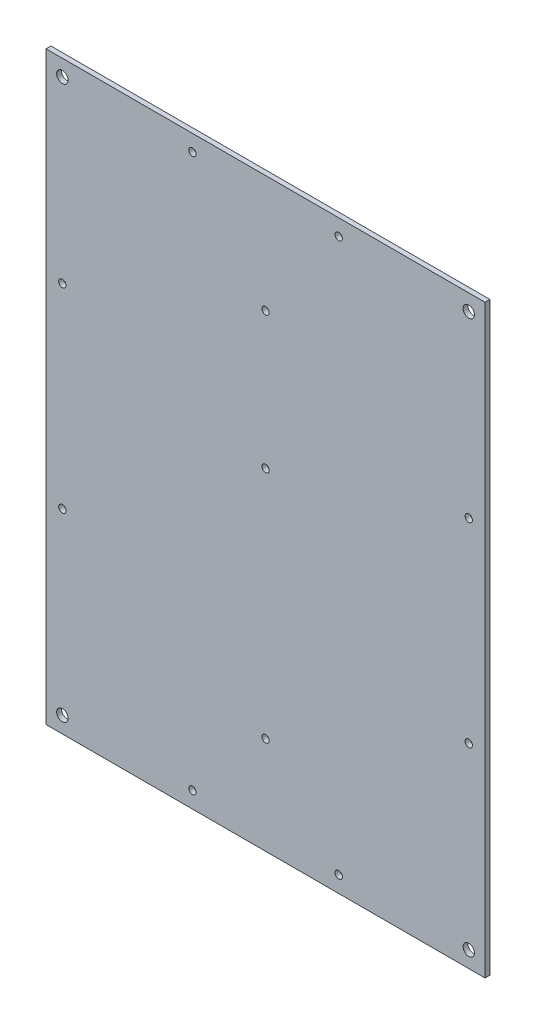
SolidWorks part; units mm, degrees
ref_plane "Спереди" through (0, 0, 0) normal (0, 0, 1) x (1, 0, 0)
ref_plane "Сверху" through (0, 0, 0) normal (0, 1, 0) x (1, 0, 0)
ref_plane "Справа" through (0, 0, 0) normal (1, 0, 0) x (0, 0, -1)
sketch "Эскиз1" plane through (0, 0, 0) normal (0, 0, 1) x (1, 0, 0)
  line L0 (0, 0) -> (270, 0)
  line L1 (0, 0) -> (0, 360)
  line L2 (270, 0) -> (270, 360)
  line L3 (0, 360) -> (270, 360)
  line L4 (10, 350) -> (260, 350) construction
  line L5 (10, 350) -> (10, 10) construction
  line L6 (260, 350) -> (260, 10) construction
  line L7 (10, 10) -> (260, 10) construction
  line L8 (0, 360) -> (20, 360) construction
  line L9 (0, 360) -> (0, 340) construction
  line L10 (20, 360) -> (20, 340) construction
  line L11 (0, 340) -> (20, 340) construction
  line L12 (135, 350) -> (135, 10) construction
  line L17 (270, 360) -> (250, 360) construction
  line L18 (270, 360) -> (270, 340) construction
  line L19 (250, 360) -> (250, 340) construction
  line L20 (270, 340) -> (250, 340) construction
  circle A0 centre (90, 10) radius 2.25
  circle A1 centre (90, 350) radius 2.25
  circle A2 centre (180, 350) radius 2.25
  circle A3 centre (180, 10) radius 2.25
  circle A4 centre (10, 240) radius 2.25
  circle A5 centre (10, 120) radius 2.25
  circle A6 centre (260, 240) radius 2.25
  circle A7 centre (260, 120) radius 2.25
  dimension "D9" = 90
  dimension "D10" = 90
  dimension "D11" = 4.5
  dimension "D12" = 90
  dimension "D13" = 4.5
  dimension "D14" = 70
  dimension "D15" = 4.5
  dimension "D16" = 4.5
  dimension "D20" = 4.5
  dimension "D21" = 120
  dimension "D22" = 120
  dimension "D23" = 120
  dimension "D24" = 4.5
  dimension "D25" = 4.5
  dimension "D26" = 120
  dimension "D27" = 120
  dimension "D19" = 4.5
  dimension "D1" = 360
  dimension "D2" = 270
  dimension "D3" = 10
  dimension "D4" = 10
  dimension "D5" = 10
  dimension "D6" = 10
  dimension "D7" = 20
  dimension "D8" = 20
  dimension "D18" = 90
  dimension "D28" = 20
  dimension "D29" = 20
  dimension "D17" = 90
extrude "Бобышка-Вытянуть1" add sketch "Эскиз1" along normal blind 3
sketch "Эскиз2" plane through (0, 0, 3) normal (0, 0, 1) x (1, 0, 0)
  line L0 (270, 360) -> (0, 360) construction
  line L1 (0, 360) -> (0, 0) construction
  line L2 (10, 350) -> (260, 350) construction
  line L3 (10, 350) -> (10, 10) construction
  line L4 (260, 350) -> (260, 10) construction
  line L5 (10, 10) -> (260, 10) construction
  line L6 (270, 0) -> (270, 360) construction
  line L7 (0, 0) -> (270, 0) construction
  circle A0 centre (10, 350) radius 3.5
  circle A1 centre (260, 350) radius 3.5
  circle A2 centre (260, 10) radius 3.5
  circle A3 centre (10, 10) radius 3.5
  dimension "D1" = 10
  dimension "D2" = 10
  dimension "D3" = 7
  dimension "D4" = 10
  dimension "D6" = 7
  dimension "D7" = 7
  dimension "D8" = 7
  dimension "D5" = 10
extrude "Вырез-Вытянуть1" cut sketch "Эскиз2" against normal through all
sketch "Sketch1" plane through (0, 0, 0) normal (0, 0, -1) x (-1, 0, 0)
  line L0 (-20, 50) -> (-250, 50) construction
  line L1 (-20, 50) -> (-250, 50) construction
  line L2 (-20, 194) -> (-250, 194) construction
  line L3 (-20, 194) -> (-250, 194) construction
  line L4 (-20, 278) -> (-250, 278) construction
  line L5 (-20, 278) -> (-250, 278) construction
  line L6 (-135, 50) -> (-135, 288) construction
  circle A0 centre (-135, 60) radius 2.25
  circle A1 centre (-135, 204) radius 2.25
  circle A2 centre (-135, 288) radius 2.25
  dimension "D3" = 10
  dimension "D4" = 4.5
  dimension "D5" = 4.5
  dimension "D6" = 4.5
  dimension "D1" = 10
  dimension "D2" = 10
extrude "Cut-Extrude1" cut sketch "Sketch1" against normal through all
